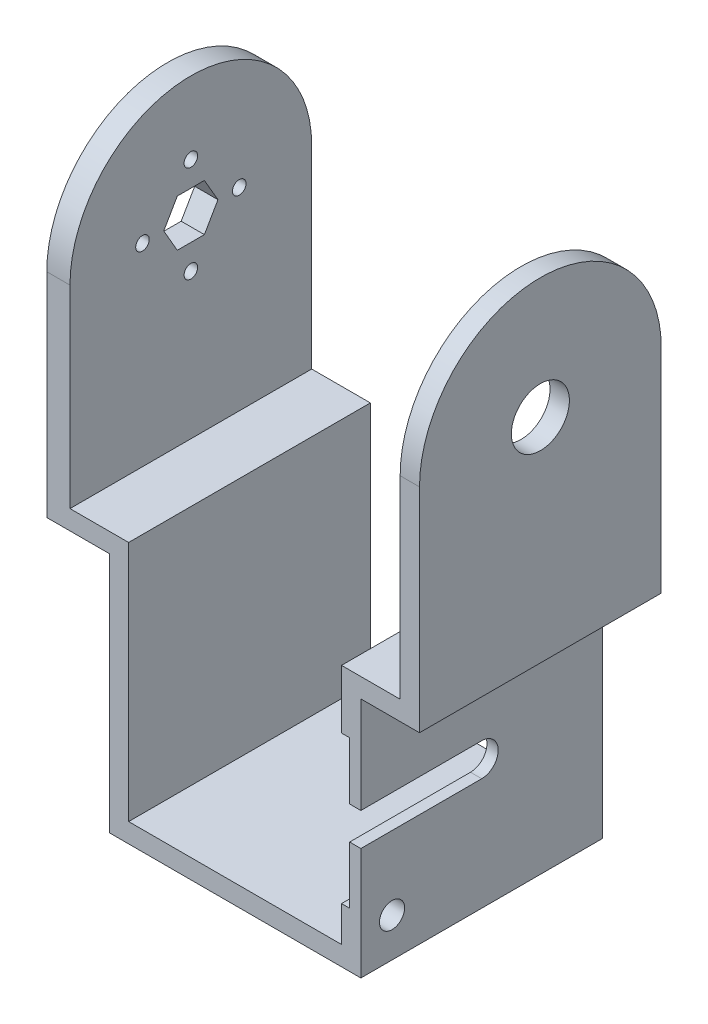
SolidWorks part; units mm, degrees
ref_plane "Front Plane" through (0, 0, 0) normal (0, 0, 1) x (1, 0, 0)
ref_plane "Top Plane" through (0, 0, 0) normal (0, 1, 0) x (1, 0, 0)
ref_plane "Right Plane" through (0, 0, 0) normal (1, 0, 0) x (0, 0, -1)
sketch "Sketch1" plane through (0, 0, 0) normal (0, 1, 0) x (1, 0, 0)
  line L0 (0, 0) -> (27.5, 0)
  line L1 (0, 0) -> (-27.5, 0)
  line L2 (-27.5, 0) -> (-27.5, 31.225)
  line L3 (-27.5, 31.225) -> (27.5, 31.225)
  line L4 (27.5, 31.225) -> (27.5, -31.225)
  line L5 (27.5, -31.225) -> (-27.5, -31.225)
  line L6 (-27.5, -31.225) -> (-27.5, 0)
  dimension "D1" = 27.5
  dimension "D2" = 27.5
  dimension "D3" = 31.225
  dimension "D4" = 62.45
extrude "Boss-Extrude1" add sketch "Sketch1" against normal blind 5 contours L2 L3 L4 L5 L6
sketch "Sketch2" plane through (0, -5, 0) normal (0, -1, 0) x (1, 0, 0)
  line L0 (27.5, 31.225) -> (32.5, 31.225)
  line L1 (27.5, -31.225) -> (32.5, -31.225)
  line L2 (32.5, -31.225) -> (32.5, 31.225)
  line L3 (27.5, 31.225) -> (27.5, -31.225)
  line L4 (-27.5, 31.225) -> (-27.5, -31.225)
  line L5 (-27.5, -31.225) -> (-32.5, -31.225)
  line L6 (-32.5, -31.225) -> (-32.5, 31.225)
  line L7 (-32.5, 31.225) -> (-27.5, 31.225)
  line L8 (0, 0) -> (-27.5, 0) construction
  dimension "D1" = 5
  dimension "D2" = 5
extrude "Boss-Extrude2" add sketch "Sketch2" against normal blind 67.45
sketch "Sketch6" plane through (27.5, 0, 0) normal (-1, 0, 0) x (0, 0, 1)
  line L0 (31.225, 62.45) -> (31.225, 0) construction
  line L1 (-31.225, 62.45) -> (-31.225, 0) construction
  line L2 (-31.225, 0) -> (31.225, 0) construction
  line L3 (31.225, 62.45) -> (-31.225, 62.45) construction
  circle A0 centre (-23.175, 51.4) radius 3.25
  circle A1 centre (23.175, 5.05) radius 3.25
  dimension "D1" = 6.5
  dimension "D2" = 6.5
  dimension "D3" = 8.05
  dimension "D4" = 8.05
  dimension "D5" = 5.05
  dimension "D6" = 11.05
extrude "Cut-Extrude4" cut sketch "Sketch6" against normal up to surface (5 mm away) up to face at (32.5, 28.725, 0)
sketch "Sketch7" plane through (27.5, 0, 0) normal (-1, 0, 0) x (0, 0, 1)
  line L0 (0, 62.45) -> (0, 0)
  line L1 (31.225, 62.45) -> (-31.225, 62.45) construction
  line L2 (-31.225, 0) -> (31.225, 0) construction
  line L3 (0, 62.45) -> (0, 28.225)
  line L4 (0, 47.3) -> (31.225, 47.3)
  line L5 (31.225, 62.45) -> (31.225, 0) construction
  line L6 (0, 9.15) -> (31.225, 9.15)
  line L7 (31.225, 9.15) -> (31.225, 47.3)
  line L8 (0, 32.475) -> (31.225, 32.475)
  line L9 (31.225, 32.475) -> (31.225, 23.975)
  line L10 (31.225, 23.975) -> (0, 23.975)
  arc A0 (0, 47.3) -> (0, 9.15) centre (0, 28.225) ccw
  arc A1 (0, 32.475) -> (0, 23.975) centre (0, 28.225) ccw
  dimension "D1" = 34.225
  dimension "D2" = 38.15
  dimension "D3" = 8.5
  dimension "D4" = 8.5
extrude "Cut-Extrude5" cut sketch "Sketch7" against normal blind 2.1 contours L4 L7 L6 A0
extrude "Cut-Extrude6" cut sketch "Sketch7<3>" against normal up to surface (5 mm away) contours L8 L9 L10 A1 up to face at (32.5, 51.4, -26.425)
sketch "Sketch7<3>" plane through (27.5, 0, 0) normal (-1, 0, 0) x (0, 0, 1) same geometry as "Sketch7"
sketch "Sketch8" plane through (0, 0, -31.225) normal (0, 0, -1) x (-1, 0, 0)
  line L3 (42.65, 62.45) -> (42.65, 112.45)
  line L4 (-42.65, 62.45) -> (-42.65, 112.45)
  line L5 (27.5, 62.45) -> (27.5, 57.45)
  line L6 (27.5, 62.45) -> (27.5, 0) construction
  line L7 (27.5, 57.45) -> (42.65, 57.45)
  line L8 (42.65, 57.45) -> (42.65, 62.45)
  line L9 (42.65, 62.45) -> (27.5, 62.45)
  line L10 (-27.5, 62.45) -> (-27.5, 57.45)
  line L11 (-27.5, 62.45) -> (-27.5, 0) construction
  line L12 (-27.5, 57.45) -> (-42.65, 57.45)
  line L13 (-42.65, 57.45) -> (-42.65, 62.45)
  line L14 (-42.65, 62.45) -> (-27.5, 62.45)
  dimension "D1" = 15.15
  dimension "D2" = 15.15
  dimension "D3" = 50
  dimension "D4" = 50
  dimension "D5" = 5
  dimension "D6" = 5
extrude "Boss-Extrude3" add sketch "Sketch8" against normal up to surface (62.45 mm away) contours L9 L5 L7 L8 | L14 L10 L12 L13 up to face at (5.92, 18.115, 31.225)
sketch "Sketch9" plane through (-42.65, 0, 0) normal (-1, 0, 0) x (0, 0, 1)
  line L0 (-31.225, 57.45) -> (-31.225, 112.45)
  line L1 (31.225, 57.45) -> (31.225, 112.45)
  line L2 (31.225, 112.45) -> (-31.225, 112.45)
  line L3 (-31.225, 57.45) -> (31.225, 57.45)
  dimension "D1" = 55
  dimension "D2" = 55
extrude "Boss-Extrude4" add sketch "Sketch9" along normal blind 6
sketch "Sketch10" plane through (42.65, 0, 0) normal (1, 0, 0) x (0, 0, -1)
  line L0 (31.225, 57.45) -> (31.225, 112.45)
  line L1 (31.225, 112.45) -> (31.225, 62.45) construction
  line L2 (31.225, 112.45) -> (-31.225, 112.45)
  line L3 (-31.225, 112.45) -> (-31.225, 57.45)
  line L4 (-31.225, 57.45) -> (31.225, 57.45)
  dimension "D1" = 55
extrude "Boss-Extrude5" add sketch "Sketch10" along normal blind 5
sketch "Sketch11" plane through (-42.65, 0, 0) normal (1, 0, 0) x (0, 0, -1)
  line L1 (-31.225, 112.45) -> (31.225, 112.45)
  arc A1 (31.225, 112.45) -> (-31.225, 112.45) centre (0, 112.45) ccw
extrude "Boss-Extrude6" add sketch "Sketch11" against normal blind 6
sketch "Sketch12" plane through (-42.65, 0, 0) normal (1, 0, 0) x (0, 0, -1)
  line L1 (7, 112.45) -> (3.5, 118.5122)
  line L2 (3.5, 118.5122) -> (-3.5, 118.5122)
  line L3 (-3.5, 118.5122) -> (-7, 112.45)
  line L4 (-7, 112.45) -> (-3.5, 106.3878)
  line L5 (-3.5, 106.3878) -> (3.5, 106.3878)
  line L6 (3.5, 106.3878) -> (7, 112.45)
  circle A0 centre (0, 112.45) radius 7 construction
  circle A1 centre (0, 112.45) radius 12.5
  circle A2 centre (0, 124.95) radius 1.75
  circle A3 centre (-12.5, 112.45) radius 1.75
  circle A4 centre (0, 99.95) radius 1.75
  circle A5 centre (12.5, 112.45) radius 1.75
  dimension "D1" = 14
  dimension "D2" = 25
  dimension "D3" = 3.5
  dimension "D4" = 3.5
  dimension "D5" = 3.5
  dimension "D6" = 3.5
extrude "Cut-Extrude7" cut sketch "Sketch12" against normal up to surface (6 mm away) contours L1 L2 L3 L4 L5 L6 up to face at (-48.65, 92.7562, 0)
sketch "Sketch13" plane through (42.65, 0, 0) normal (-1, 0, 0) x (0, 0, 1)
  line L0 (-31.225, 112.45) -> (31.225, 112.45)
  arc A0 (31.225, 112.45) -> (-31.225, 112.45) centre (0, 112.45) ccw
extrude "Boss-Extrude7" add sketch "Sketch13" against normal blind 5
sketch "Sketch14" plane through (42.65, 0, 0) normal (-1, 0, 0) x (0, 0, 1)
  circle A0 centre (0, 112.45) radius 7.5
  dimension "D1" = 15
extrude "Cut-Extrude8" cut sketch "Sketch14" against normal up to surface (5 mm away) contours A0 up to face at (47.65, 92.7562, 0)
extrude "Cut-Extrude9" cut sketch "Sketch12<3>" against normal up to surface (6 mm away) contours A4 | A3 | A2 | A5 up to face at (-48.65, 112.45, 0)
sketch "Sketch12<3>" plane through (-42.65, 0, 0) normal (1, 0, 0) x (0, 0, -1) same geometry as "Sketch12"
sketch "Sketch16" plane through (-27.5, 0, 0) normal (1, 0, 0) x (0, 0, -1)
  line L0 (0, 62.45) -> (0, 28.22)
  line L1 (31.225, 62.45) -> (-31.225, 62.45) construction
  circle A0 centre (0, 28.22) radius 3
  dimension "D2" = 6
  dimension "D1" = 34.23
extrude "Boss-Extrude8" add sketch "Sketch16" against normal blind 17 contours A0
